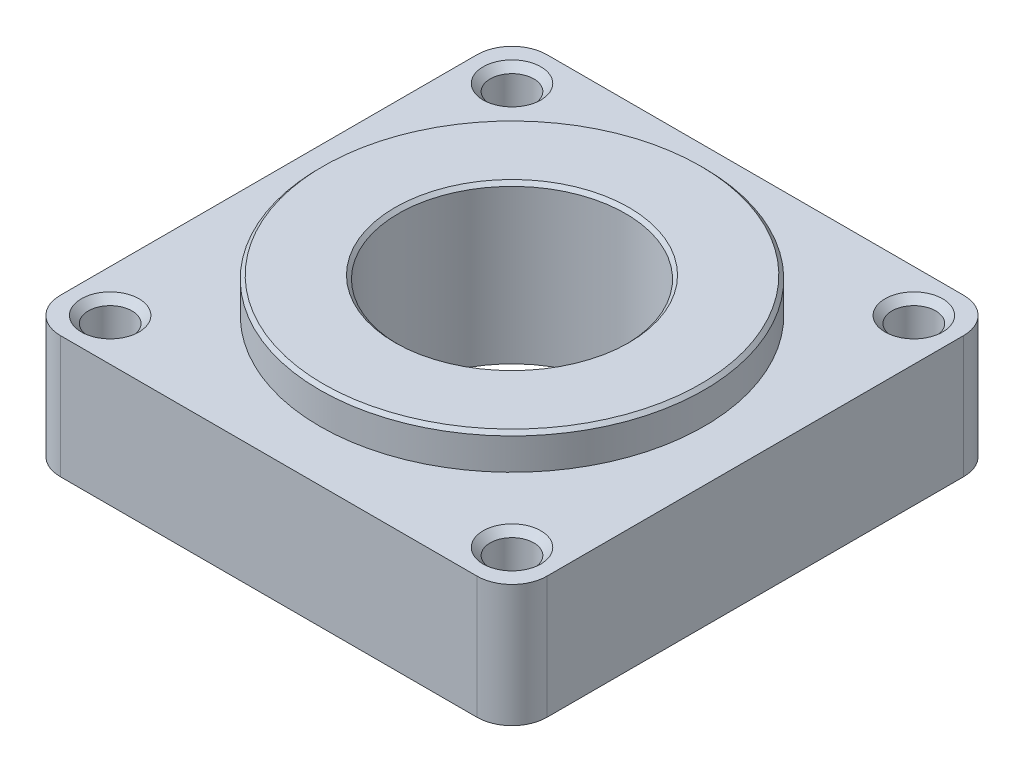
SolidWorks part; units mm, degrees
ref_plane "Спереди" through (0, 0, 0) normal (0, 0, 1) x (1, 0, 0)
ref_plane "Сверху" through (0, 0, 0) normal (0, 1, 0) x (1, 0, 0)
ref_plane "Справа" through (0, 0, 0) normal (1, 0, 0) x (0, 0, -1)
sketch "Эскиз1" plane through (0, 0, 0) normal (0, 1, 0) x (1, 0, 0)
  line L0 (-13.925, 13.925) -> (13.925, 13.925)
  line L1 (-13.925, 13.925) -> (-13.925, -13.925)
  line L2 (-13.925, -13.925) -> (-13.925, 13.925) construction
  line L3 (13.925, 13.925) -> (13.925, -13.925)
  line L5 (13.925, -13.925) -> (-13.925, -13.925)
  line L7 (-11.5, -11.5) -> (11.5, -11.5) construction
  line L8 (-11.5, -11.5) -> (-11.5, 11.5) construction
  line L9 (-11.5, 11.5) -> (11.5, 11.5) construction
  line L10 (11.5, -11.5) -> (11.5, 11.5) construction
  line L11 (-11.5, -11.5) -> (11.5, 11.5) construction
  line L12 (-11.5, 11.5) -> (11.5, -11.5) construction
  circle A0 centre (-11.5, 11.5) radius 1.25
  circle A1 centre (11.5, 11.5) radius 1.25
  circle A2 centre (-11.5, -11.5) radius 1.25
  circle A3 centre (11.5, -11.5) radius 1.25
  circle A9 centre (0, 0) radius 11
  circle A10 centre (0, 0) radius 6.5
  point P0 (0, 0)
  point P2 (-13.925, 0)
  point P8 (0, 0)
  point P27 (0, 13.925)
  dimension "D1" = 27.85
  dimension "D2" = 27.85
  dimension "D5" = 27.85
  dimension "D3" = 23
extrude "Бобышка-Вытянуть1" add sketch "Эскиз1" along normal blind 7 contours L3 L0 L1 L5 A10 A9 | A2 | A3 | A9 A0 region at (0, 0, -13.5311) region at (-10.6889, 0, 0)
extrude "Бобышка-Вытянуть3" add sketch "Эскиз1<5>" along normal blind 9 contours A9 A10 region at (-10.6889, 0, 0)
sketch "Эскиз1<5>" plane through (0, 0, 0) normal (0, 1, 0) x (1, 0, 0) same geometry as "Эскиз1"
chamfer "Фаска2" distance 0.4 angle 45 4 edges at (11.5, 7, -10.25) (-11.5, 7, -10.25) (11.5, 7, 12.75) (-11.5, 7, 12.75)
chamfer "Фаска3" distance 0.2 angle 45 2 edges at (0, 9, 11) (0, 9, 6.5)
fillet "Скругление1" radius 2 4 edges at (-13.925, 3.5, 13.925) (-13.925, 3.5, -13.925) (13.925, 3.5, -13.925) (13.925, 3.5, 13.925)
